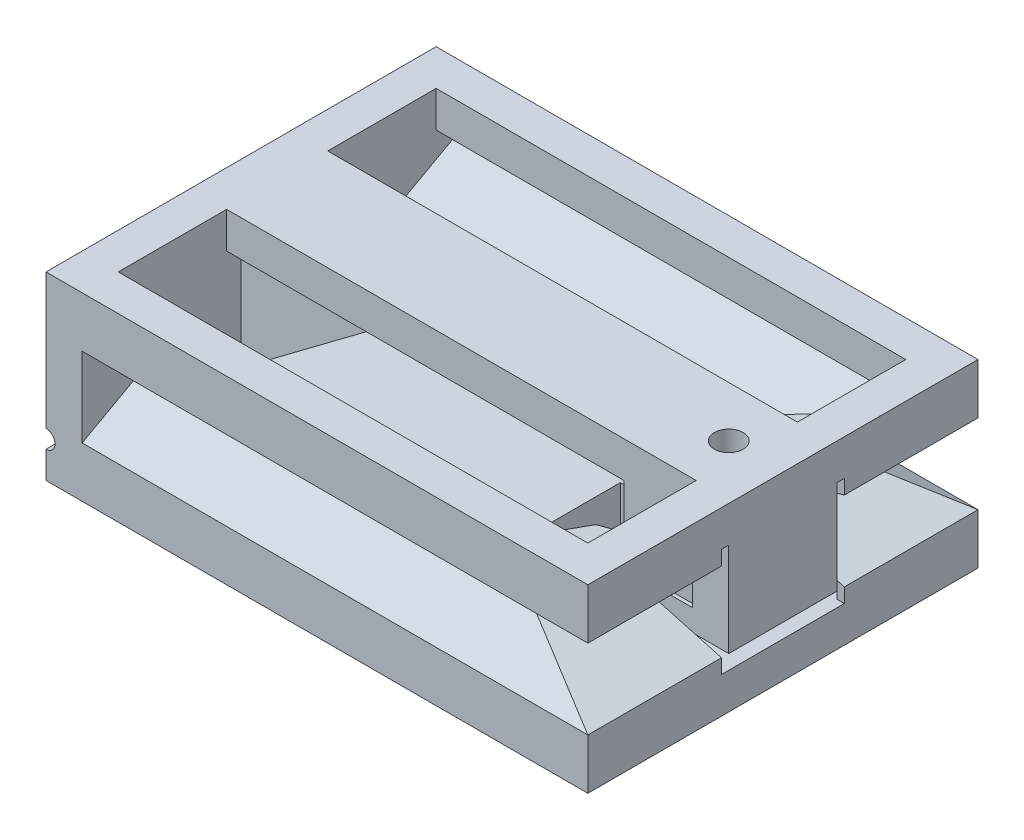
SolidWorks part; units mm, degrees
ref_plane "Front Plane" through (0, 0, 0) normal (0, 0, 1) x (1, 0, 0)
ref_plane "Top Plane" through (0, 0, 0) normal (0, 1, 0) x (1, 0, 0)
ref_plane "Right Plane" through (0, 0, 0) normal (1, 0, 0) x (0, 0, -1)
sketch "Sketch1" plane through (0, 0, 0) normal (0, 0, 1) x (1, 0, 0)
  line L0 (0, 0) -> (7, 0)
  line L1 (0, 0) -> (0, -1.5)
  line L2 (0, -1.5) -> (7, -1.5)
  line L3 (7, 0) -> (7, 0.5)
  line L4 (7, 0.5) -> (-0.5, 0.5)
  line L5 (-0.5, 0.5) -> (-0.5, -2)
  line L6 (-0.5, -2) -> (7, -2)
  line L7 (7, -2) -> (7, -1.5)
  dimension "D1" = 7
  dimension "D2" = 1.5
  dimension "D3" = 0.5
  dimension "D4" = 0.5
  dimension "0.5" = 0.5
extrude "Base shape" add sketch "Sketch1" along normal blind 2.7 and the other way blind 2.7
sketch "Sketch12" plane through (0, 0, 0) normal (0, 0, 1) x (1, 0, 0)
  line L0 (0, 0) -> (2, 0)
  line L1 (0, 0) -> (7, 0) construction
  line L2 (2, 0) -> (0, -1.5)
  line L3 (0, -1.5) -> (0, 0)
  dimension "D1" = 2
extrude "Hinge stabilizer" add sketch "Sketch12" along normal blind 0.5 and the other way blind 0.5
sketch "Sketch2" plane through (0, 0.5, 0) normal (0, 1, 0) x (1, 0, 0)
  line L0 (7, -2.7) -> (7, 2.7) construction
  line L1 (5.5, -0.75) -> (7, -0.75)
  line L2 (5.5, -0.75) -> (5.5, 0.75)
  line L3 (5.5, 0.75) -> (7, 0.75)
  line L4 (7, -0.75) -> (7, 0.75)
  line L5 (5.5, -0.75) -> (7, 0.75) construction
  line L6 (5.5, 0.75) -> (7, -0.75) construction
  point P0 (6.25, 0)
  point P7 (7, 0)
  dimension "D1" = 1.5
extrude "Drive screw housing" add sketch "Sketch2" against normal blind 1.8
sketch "Sketch4" plane through (0, -1.3, 0) normal (0, -1, 0) x (1, 0, 0)
  line L0 (7, 0.75) -> (7, -0.75) construction
  line L1 (5.5, 0.75) -> (7, 0.75) construction
  circle A0 centre (6.25, 0) radius 0.2
  point P4 (7, 0)
  point P7 (6.25, 0.75)
  dimension "D1" = 0.4
extrude "screw thread" cut sketch "Sketch4" against normal blind 11.5
sketch "Sketch5" plane through (0, 0.5, 0) normal (0, 1, 0) x (1, 0, 0)
  line L0 (-0.5, -2.7) -> (-0.5, 2.7) construction
  line L1 (0, 2.2) -> (6.5, 2.2)
  line L2 (0, 2.2) -> (0, 0.7)
  line L3 (0, 0.7) -> (6.5, 0.7)
  line L4 (6.5, 2.2) -> (6.5, 0.7)
  line L5 (0, -0.7) -> (6.5, -0.7)
  line L6 (0, -0.7) -> (0, -2.2)
  line L7 (0, -2.2) -> (6.5, -2.2)
  line L8 (6.5, -0.7) -> (6.5, -2.2)
  line L9 (7, -2.7) -> (7, 2.7) construction
  line L10 (7, 2.7) -> (-0.5, 2.7) construction
  line L11 (7, -2.7) -> (-0.5, -2.7) construction
  dimension "D1" = 0.5
  dimension "D2" = 0.5
  dimension "D3" = 0.5
  dimension "D4" = 0.5
  dimension "D5" = 1.5
extrude "goldpin/loading cutout" cut sketch "Sketch5" against normal blind 1.5
sketch "Sketch6" plane through (0, -2, 0) normal (0, -1, 0) x (1, 0, 0)
  line L0 (7, 2.7) -> (7, -2.7) construction
  line L1 (4, 0.75) -> (5.5, 0.75)
  line L2 (4, 0.75) -> (4, -0.75)
  line L3 (4, -0.75) -> (5.5, -0.75)
  line L4 (5.5, 0.75) -> (5.5, -0.75)
  line L5 (4, 0.75) -> (5.5, -0.75) construction
  line L6 (4, -0.75) -> (5.5, 0.75) construction
  line L7 (7, -2.7) -> (7, 2.7) construction
  point P0 (4.75, 0)
  point P7 (7, 0)
  dimension "D1" = 1.5
  dimension "D2" = 1.5
extrude "Trodes exit" cut sketch "Sketch6" against normal blind 0.5
sketch "Sketch7" plane through (0, 0, 2.7) normal (0, 0, 1) x (1, 0, 0)
  line L0 (7, 0) -> (7, -0.2)
  line L1 (7, -1.3) -> (7, 0) construction
  line L3 (7, -1.5) -> (7, -1.3)
  line L17 (7, -0.2) -> (5, -0.75)
  line L18 (5, -0.75) -> (7, -1.3)
  line L24 (6.9, 0) -> (6.9, -0.1238)
  line L25 (6.9, -0.1238) -> (4.6229, -0.75)
  line L26 (4.6229, -0.75) -> (6.9, -1.3762)
  line L27 (6.9, -1.5) -> (6.9, -1.3762)
  line L28 (6.9, 0) -> (7, 0)
  line L29 (6.9, -1.5) -> (7, -1.5)
  dimension "D1" = 0.2
  dimension "D2" = 1.5
  dimension "D3" = 0.75
  dimension "D4" = 2
  dimension "D5" = 0.1
extrude "Front bellow" add sketch "Sketch7" against normal offset from surface (1.85 mm away) 0.85 up to plane "Front Plane"
sketch "Sketch8" plane through (7, 0, 0) normal (1, 0, 0) x (0, 0, -1)
  line L4 (-2.7, -0.2) -> (-1.7, -0.75)
  line L7 (-2.7, -0.75) -> (-2.7, -0.2) construction
  line L9 (-2.7, -1.3) -> (-1.7, -0.75)
  line L14 (-2.7, -0.2) -> (-2.9092, -0.75)
  line L15 (-2.9092, -0.75) -> (-2.7, -1.3)
  line L16 (-0.85, -0.75) -> (-2.7, -0.75) construction
  point P2 (-2.7, -0.75)
  point P3 (-1.7, -0.75)
  point P12 (-1.7, -0.75)
  point P14 (-1.7, -0.7818)
  point P15 (-2.9092, -0.75)
  dimension "D1" = 1
extrude "Side bellow cut" cut sketch "Sketch8" against normal blind 5
sketch "Sketch9" plane through (7, 0, 0) normal (1, 0, 0) x (0, 0, -1)
  line L12 (-2.7, -0.2) -> (-1.7, -0.75)
  line L23 (-2.7, 0.5) -> (-2.7, -0.2)
  line L28 (-2.7, -1.3) -> (-2.7, -2)
  line L29 (-2.6, 0.5) -> (-2.6, -0.1312)
  line L34 (-2.6, -1.3688) -> (-2.6, -2)
  line L35 (-2.7, 0.5) -> (-2.6, 0.5)
  line L36 (-2.7, -2) -> (-2.6, -2)
  line L37 (-2.6, -0.1312) -> (-1.3536, -0.6091) construction
  line L38 (-2.7, -0.2) -> (-1.729, -0.5723) construction
  line L39 (-1.3536, -0.6091) -> (-2.3757, -0.7852) construction
  line L40 (-1.729, -0.5723) -> (-2.751, -0.7484) construction
  line L41 (-2.3757, -0.7852) -> (-1.7267, -1.034) construction
  line L42 (-2.751, -0.7484) -> (-2.0061, -1.034) construction
  line L43 (-2.0061, -1.034) -> (-2.7, -1.3) construction
  line L44 (-1.7267, -1.034) -> (-2.6, -1.3688) construction
  line L45 (-1.7, -0.75) -> (-2.7, -1.3)
  line L46 (-2.6, -0.1312) -> (-1.475, -0.75)
  line L47 (-0.85, -0.75) -> (-1.7, -0.75) construction
  line L48 (-1.475, -0.75) -> (-2.6, -1.3688)
  dimension "D1" = 0.1
extrude "Side bellow" add sketch "Sketch9" along normal up to next from surface starting at face at (0, -0.25, -1.525)
chamfer "Chamfer1" distance 0.2 angle 45 2 edges at (2.3114, -0.75, 1.475) (4.6229, -0.75, 1.1625) first distance on face at (2.8739, -1.0594, 2.0375) first distance on face at (5.9837, -1.1242, 1.675)
chamfer "Chamfer2" distance 0.5 angle 45 1 edges at (4.7896, -0.7572, 0.85)
sketch "Sketch10" plane through (0, 0, 2.7) normal (0, 0, 1) x (1, 0, 0)
  line L0 (-0.5, 0.5) -> (-0.5, -2) construction
  circle A0 centre (-0.5, -1.5) radius 0.125
  dimension "D2" = 0.25
  dimension "D1" = 0.5
extrude "Back hinge" cut sketch "Sketch10" against normal through all
mirror "Mirror1" about plane through (0, 0, 0) normal (0, 0, 1) of "Side bellow cut", "Side bellow", "Chamfer1", "Chamfer2", "Front bellow"
